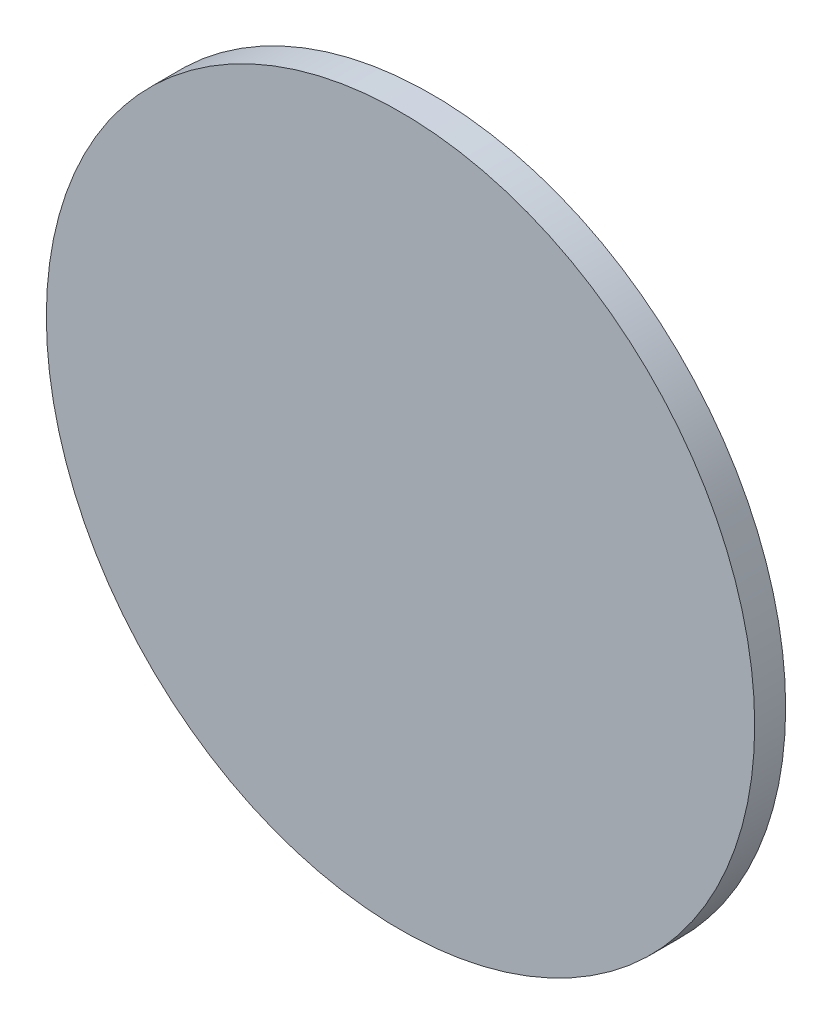
SolidWorks part; units mm, degrees
ref_plane "Front Plane" through (0, 0, 0) normal (0, 0, 1) x (1, 0, 0)
ref_plane "Top Plane" through (0, 0, 0) normal (0, 1, 0) x (1, 0, 0)
ref_plane "Right Plane" through (0, 0, 0) normal (1, 0, 0) x (0, 0, -1)
sketch "Sketch1" plane through (0, 0, 0) normal (0, 0, 1) x (1, 0, 0)
  circle A0 centre (0, 0) radius 36.3093
  dimension "D1" = 72.6186
extrude "Boss-Extrude1" add sketch "Sketch1" along normal blind 3.175
